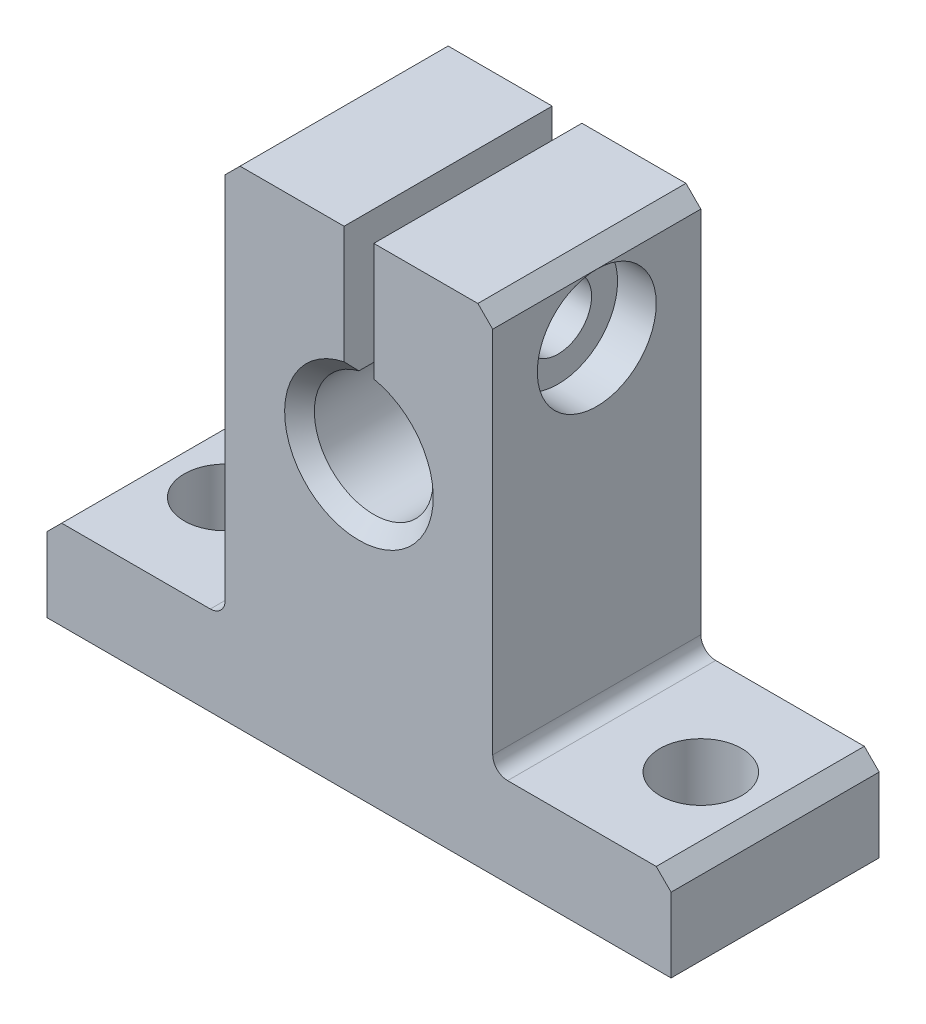
SolidWorks part; units mm, degrees
material "Lega 1060"
ref_plane "Piano frontale" through (0, 0, 0) normal (0, 0, 1) x (1, 0, 0)
ref_plane "Piano superiore" through (0, 0, 0) normal (0, 1, 0) x (1, 0, 0)
ref_plane "Piano destro" through (0, 0, 0) normal (1, 0, 0) x (0, 0, -1)
ref_plane "Piano1" through (0, 0, -7) normal (0, 0, -1) x (-1, 0, 0)
sketch "Schizzo10" plane through (0, 0, 0) normal (0, 0, 1) x (1, 0, 0)
  line L0 (21, 0) -> (-21, 0)
  line L1 (-21, 0) -> (-21, 6)
  line L2 (-21, 6) -> (-9, 6)
  line L3 (-9, 6) -> (-9, 32.8)
  line L4 (-9, 32.8) -> (-1, 32.8)
  line L5 (-1, 32.8) -> (-1, 23.873)
  line L6 (0, -6.3586) -> (0, 69.8144) construction
  line L7 (1, 32.8) -> (1, 23.873)
  line L8 (9, 32.8) -> (1, 32.8)
  line L9 (9, 6) -> (9, 32.8)
  line L10 (21, 6) -> (9, 6)
  line L11 (21, 0) -> (21, 6)
  arc A0 (-1, 23.873) -> (1, 23.873) centre (0, 20) ccw
  point P13 (0, 0)
  dimension "D1" = 8
  dimension "D2" = 42
  dimension "D3" = 6
  dimension "D4" = 18
  dimension "D5" = 20
  dimension "D6" = 32.8
  dimension "D7" = 2
extrude "Estrusione-Estrusione2" add sketch "Schizzo10" along normal blind 14
hole_wizard "Foro Ø5.5 (5.5)-3" positions "Schizzo12" profile "Schizzo11" hole size "Ø5.5" standard "ISO" end condition through all
sketch "Schizzo12" plane through (0, 6, 0) normal (0, 1, 0) x (1, 0, 0)
  line L0 (-17.0222, -7) -> (18.382, -7) construction
  line L2 (-9, 0) -> (-21, 0) construction
  line L3 (-9, -14) -> (-21, -14) construction
  point P0 (-16, -7)
  point P2 (16, -7)
  dimension "D1" = 32
  dimension "D2" = 16
sketch "Schizzo11" plane through (-16, 6, 7) normal (1, 0, 0) x (0, 0, 1)
  line L0 (0, 0) -> (0, 6)
  line L1 (0, 6) -> (2.75, 6)
  line L2 (2.75, 6) -> (2.75, 0)
  line L5 (2.75, 0) -> (0, 0)
  line L11 (0, -6.35) -> (0, 107.95) construction
  dimension "Thru Hole Dia." = 5.5
  dimension "Thru Hole Depth" = 6
hole_wizard "Foro lamato per Vite M4 a testa cilindrica piana-1" positions "Schizzo14" profile "Schizzo13" counterbore size "M4" standard "ISO" end condition up to next
sketch "Schizzo14" plane through (9, 0, 0) normal (1, 0, 0) x (0, 0, -1)
  line L0 (-7, 20.4964) -> (-7, 29.1822) construction
  line L2 (-14, 6) -> (-14, 32.8) construction
  line L3 (0, 6) -> (0, 32.8) construction
  line L4 (-14, 32.8) -> (0, 32.8) construction
  point P0 (-7, 27.8)
  dimension "D1" = 5
sketch "Schizzo13" plane through (9, 27.8, 7) normal (0, 1, 0) x (0, 0, -1)
  line L0 (0, 0) -> (0, 8)
  line L1 (0, 8) -> (2.25, 8)
  line L3 (2.25, 8) -> (2.25, 2.6)
  line L4 (2.25, 2.6) -> (4, 2.6)
  line L5 (4, 2.6) -> (4, 0)
  line L7 (4, 0) -> (0, 0)
  line L11 (0, -6.35) -> (0, 107.95) construction
  dimension "Thru Hole Dia." = 4.5
  dimension "Thru Hole Depth" = 8
  dimension "C'Bore Dia." = 8
  dimension "C'Bore Depth" = 2.6
hole_wizard "Foro filettato M4-1" positions "Schizzo16" profile "Schizzo15" tap size "M4" standard "ISO" end condition through all
sketch "Schizzo16" plane through (-1, 0, 0) normal (1, 0, 0) x (0, 0, -1)
  circle A0 centre (-7, 27.8) radius 2.25 construction
  point P0 (-7, 27.8)
sketch "Schizzo15" plane through (-1, 27.8, 7) normal (0, 1, 0) x (0, 0, -1)
  line L0 (0, 0) -> (0, 20)
  line L1 (0, 20) -> (1.65, 20)
  line L2 (1.65, 20) -> (1.65, 0.2165)
  line L3 (1.65, 0.2165) -> (2.025, 0)
  line L5 (2.025, 0) -> (0, 0)
  line L6 (-1.65, 0.2165) -> (-2.025, 0) construction
  line L11 (0, -6.35) -> (0, 107.95) construction
  dimension "Thread Major Dia." = 3.3
  dimension "Thru Tap Drill Depth" = 20
  dimension "Near C'Sink Dia." = 4.05
  dimension "Near C'Sink Angle" = 120
fillet "Raccordo1" radius 1 2 edges at (-9, 6, 7) (9, 6, 7)
chamfer "Smusso1" distance 1 angle 45 6 edges at (0, 16, 0) (0, 16, 14) (-9, 32.8, 7) (9, 32.8, 7) (-21, 6, 7) (21, 6, 7)
